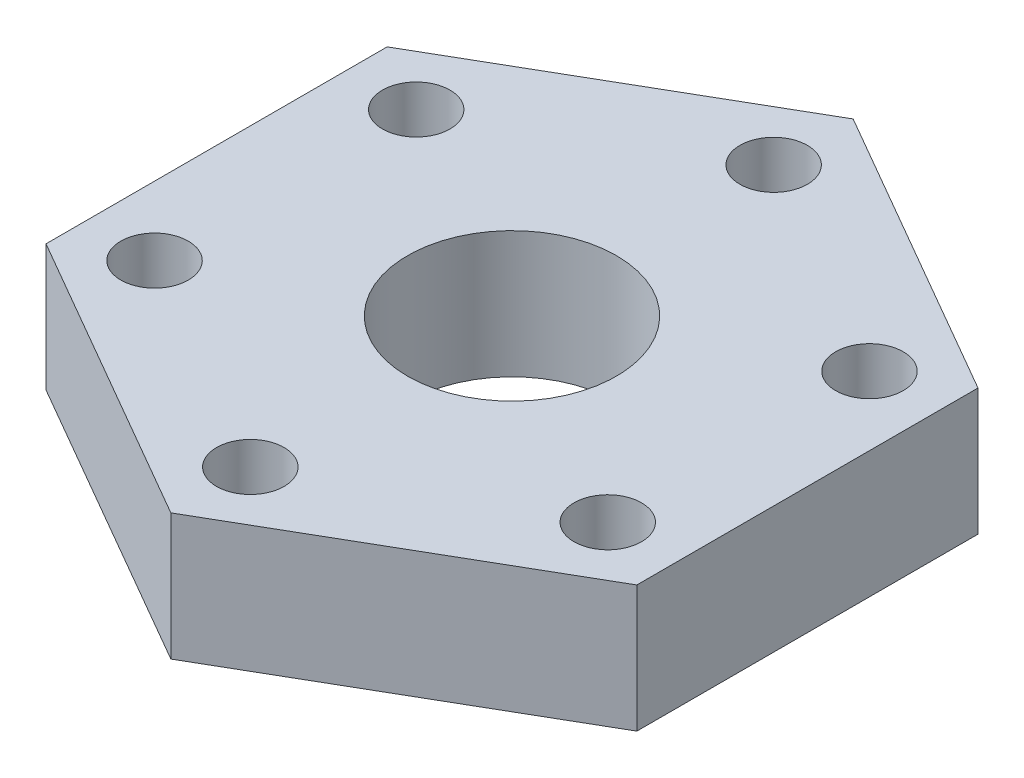
SolidWorks part; units mm, degrees
ref_plane "Front Plane" through (0, 0, 0) normal (0, 0, 1) x (1, 0, 0)
ref_plane "Top Plane" through (0, 0, 0) normal (0, 1, 0) x (1, 0, 0)
ref_plane "Right Plane" through (0, 0, 0) normal (1, 0, 0) x (0, 0, -1)
sketch "Sketch1" plane through (0, 0, 0) normal (0, 1, 0) x (1, 0, 0)
  line L0 (-7, -4.0415) -> (0, -8.0829) construction
  line L1 (0, -8.0829) -> (7, -4.0415) construction
  line L2 (7, -4.0415) -> (7, 4.0415) construction
  line L3 (7, 4.0415) -> (0, 8.0829) construction
  line L4 (0, 8.0829) -> (-7, 4.0415) construction
  line L5 (-7, 4.0415) -> (-7, -4.0415) construction
  line L6 (-7, -4.0415) -> (0, -8.0829)
  line L7 (0, -8.0829) -> (7, -4.0415)
  line L8 (7, -4.0415) -> (7, 4.0415)
  line L9 (7, 4.0415) -> (0, 8.0829)
  line L10 (0, 8.0829) -> (-7, 4.0415)
  line L11 (-7, 4.0415) -> (-7, -4.0415)
  line L12 (0, 0) -> (-7, 4.0415) construction
  circle A0 centre (0, 0) radius 2.475
  circle A1 centre (-5.3694, 3.1) radius 0.8
  circle A2 centre (0, 0) radius 7 construction
  circle A3 centre (0, 6.2) radius 0.8
  circle A4 centre (5.3694, 3.1) radius 0.8
  circle A5 centre (5.3694, -3.1) radius 0.8
  circle A6 centre (0, -6.2) radius 0.8
  circle A7 centre (-5.3694, -3.1) radius 0.8
  circle A8 centre (0, -65.3564) radius 0.8 construction
  point P26 (0, 0)
  dimension "D1" = 4.95
  dimension "D3" = 6
extrude "Boss-Extrude1" add sketch "Sketch1" along normal blind 3
